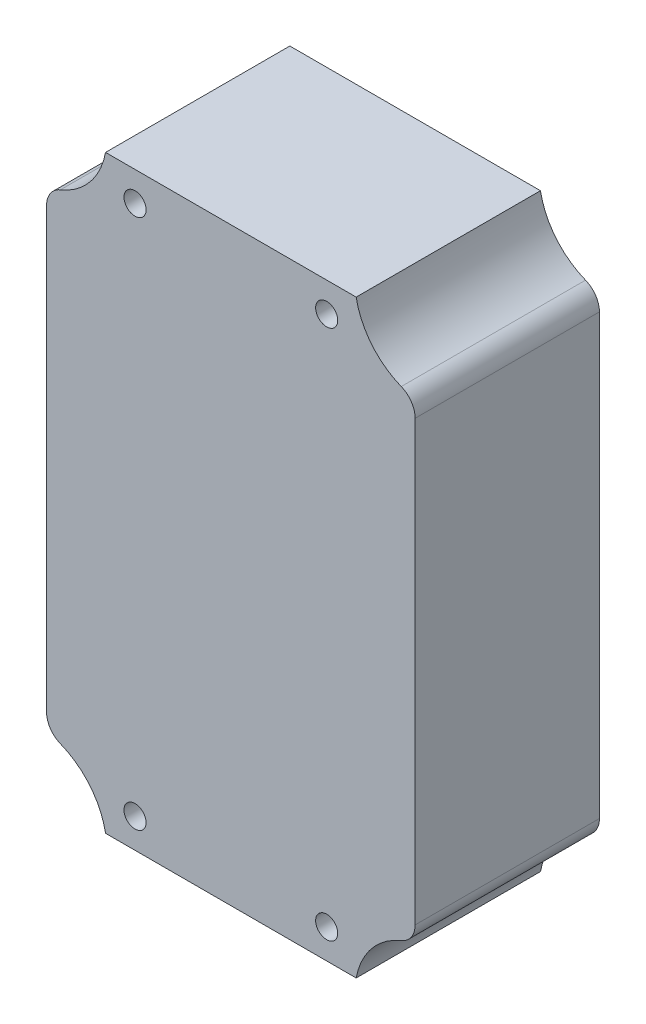
SolidWorks part; units mm, degrees
ref_plane "前视基准面" through (0, 0, 0) normal (0, 0, 1) x (1, 0, 0)
ref_plane "上视基准面" through (0, 0, 0) normal (0, 1, 0) x (1, 0, 0)
ref_plane "右视基准面" through (0, 0, 0) normal (1, 0, 0) x (0, 0, -1)
sketch "草图1" plane through (0, 0, 0) normal (0, 0, 1) x (1, 0, 0)
  line L0 (0, 0) -> (0, 40) construction
  line L1 (-17, 40) -> (17, 40)
  line L2 (-25, 32) -> (-25, -32)
  line L3 (-17, -40) -> (17, -40)
  line L4 (25, 32) -> (25, -32)
  line L5 (-25, 40) -> (25, -40) construction
  line L6 (-25, -40) -> (25, 40) construction
  line L7 (-17, 36) -> (17, 36) construction
  line L8 (0, 0) -> (25, 0) construction
  line L9 (-25, 32) -> (-17, 32)
  line L10 (-17, 40) -> (-17, 32)
  line L13 (25, 32) -> (17, 32)
  line L14 (17, 40) -> (17, 32)
  line L17 (-25, -32) -> (-17, -32)
  line L18 (-17, -40) -> (-17, -32)
  line L21 (25, -32) -> (17, -32)
  line L22 (17, -40) -> (17, -32)
  circle A0 centre (-13, 36) radius 1.5
  circle A1 centre (13, 36) radius 1.5
  circle A2 centre (-13, -36) radius 1.5
  circle A3 centre (13, -36) radius 1.5
  point P0 (0, 0)
  point P20 (-17, -36)
  dimension "D6" = 3
  dimension "D7" = 13
  dimension "D1" = 80
  dimension "D2" = 50
  dimension "D3" = 8
  dimension "D4" = 8
  dimension "D5" = 8
extrude "凸台-拉伸1" add sketch "草图1" along normal blind 25
fillet "圆角1" radius 10 4 edges at (17, 32, 12.5) (-17, 32, 12.5) (17, -32, 12.5) (-17, -32, 12.5)
fillet "圆角2" radius 3 4 edges at (25, -32, 12.5) (-25, -32, 12.5) (-25, 32, 12.5) (25, 32, 12.5)
